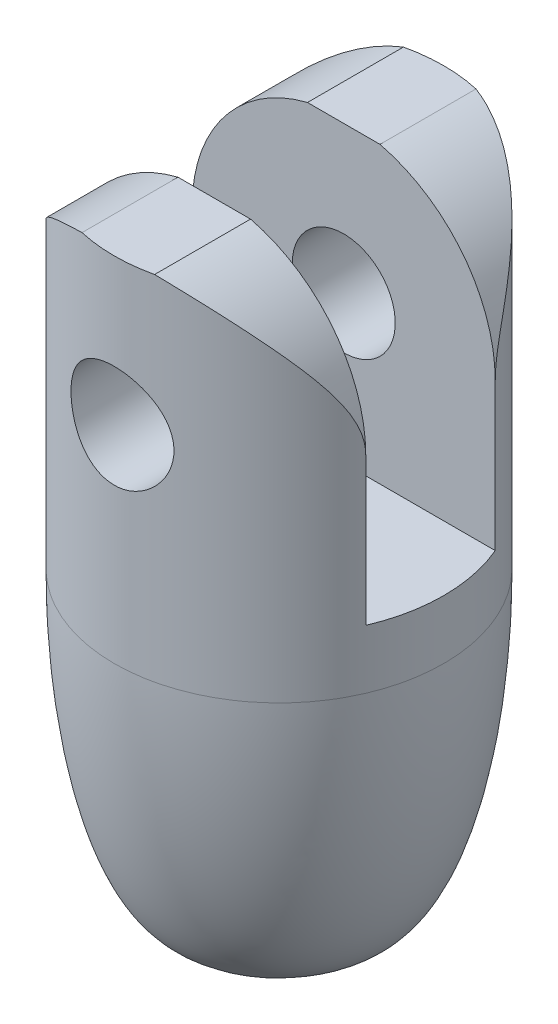
SolidWorks part; units mm, degrees
ref_plane "Front Plane" through (0, 0, 0) normal (0, 0, 1) x (1, 0, 0)
ref_plane "Top Plane" through (0, 0, 0) normal (0, 1, 0) x (1, 0, 0)
ref_plane "Right Plane" through (0, 0, 0) normal (1, 0, 0) x (0, 0, -1)
sketch "Sketch1" plane through (0, 0, 0) normal (0, 1, 0) x (1, 0, 0)
  circle A0 centre (0, 0) radius 1.6
  circle A1 centre (0, 0) radius 5.6
  dimension "D1" = 3.2
  dimension "D2" = 4
extrude "Boss-Extrude1" add sketch "Sketch1" along normal blind 10
sketch "Sketch2" plane through (0, 10, 0) normal (0, 1, 0) x (1, 0, 0)
  circle A1 centre (0, 0) radius 5.6
  circle A2 centre (0, 0) radius 5.6
  dimension "D1" = 0
extrude "Boss-Extrude2" add sketch "Sketch2" along normal blind 2
sketch "Sketch3" plane through (0, 12, 0) normal (0, 1, 0) x (1, 0, 0)
  line L0 (-5.6, 0) -> (5.6, 0) construction
  line L1 (-5.1498, 2.2) -> (5.1498, 2.2)
  line L2 (-5.1498, -2.2) -> (5.1498, -2.2)
  circle A0 centre (0, 0) radius 5.6 construction
  arc A3 (-5.1498, -2.2) -> (5.1498, -2.2) centre (0, 0) ccw
  arc A4 (5.1498, 2.2) -> (-5.1498, 2.2) centre (0, 0) ccw
  dimension "D1" = 2.2
  dimension "D2" = 2.2
extrude "Boss-Extrude3" add sketch "Sketch3" along normal blind 10
sketch "Sketch4" plane through (0, 0, 2.2) normal (0, 0, -1) x (-1, 0, 0)
  line L0 (0, 17) -> (0, 0) construction
  line L1 (5.1498, 22) -> (5.1498, 22.1)
  line L2 (-5.1498, 22) -> (-5.1498, 12) construction
  line L3 (-5.1498, 17) -> (-5.1498, 12)
  line L4 (5.1498, 22) -> (-5.1498, 22) construction
  line L5 (-5.1498, 12) -> (-5.2498, 12)
  line L6 (5.1498, 22) -> (-5.1498, 22)
  line L7 (5.1498, 22) -> (5.1498, 12) construction
  line L8 (-5.1498, 12) -> (-5.1498, 17)
  line L9 (5.1498, 17) -> (5.1498, 12)
  line L10 (-5.1498, 22.1) -> (-5.2498, 22.1)
  line L11 (-5.2498, 12) -> (-5.2498, 22.1)
  line L12 (5.1498, 12) -> (5.2498, 12)
  line L13 (5.1498, 12) -> (5.1498, 17)
  line L14 (5.1498, 22.1) -> (5.2498, 22.1)
  line L15 (5.2498, 12) -> (5.2498, 22.1)
  line L16 (-5.1498, 22) -> (-5.1498, 22.1)
  circle A1 centre (0, 17) radius 1.75
  circle A2 centre (0, 17) radius 5.1498
  dimension "D1" = 5
  dimension "D2" = 3.5
  dimension "D3" = 0.1
  dimension "D4" = 0.1
  dimension "D5" = 0.1
  dimension "D6" = 0.1
extrude "Cut-Extrude1" cut sketch "Sketch4" against normal through all both and the other way through all
fillet "Fillet1" radius 3 1 edges at (0, 0, 5.6) second distance 10 first distance on face at (0, 0, 5.6)
